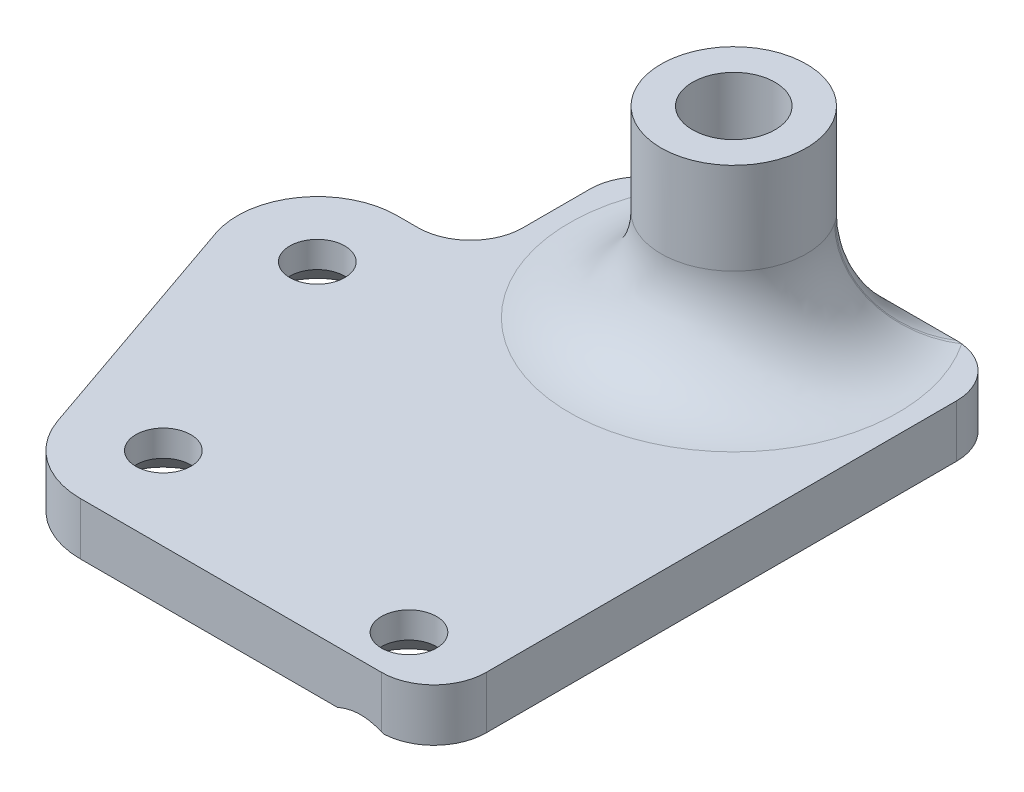
SolidWorks part; units mm, degrees
ref_plane "Front Plane" through (0, 0, 0) normal (0, 0, 1) x (1, 0, 0)
ref_plane "Top Plane" through (0, 0, 0) normal (0, 1, 0) x (1, 0, 0)
ref_plane "Right Plane" through (0, 0, 0) normal (1, 0, 0) x (0, 0, -1)
ref_axis "X-Axis" through (-88.4377, 0, 0) along (1, 0, 0)
ref_axis "Y-Axis" through (0, 0, -69.2525) along (0, 0, 1)
ref_axis "Z-Axis" through (0, -52.5493, 0) along (0, 1, 0)
sketch "Sketch1" plane through (0, 0, 0) normal (0, 1, 0) x (1, 0, 0)
  line L0 (0, 0) -> (-14, 0) construction
  line L4 (0, 0) -> (0, -10.5) construction
  line L5 (-16.8827, -0.9964) -> (-13.6961, -10.2156)
  line L6 (-11.2, 9.6) -> (2.8, 9.6)
  line L7 (-11.2, 9.6) -> (-11.2, 3.05)
  line L9 (2.8, 9.6) -> (2.8, 2.6)
  line L11 (-14, 3.05) -> (-11.2, 3.05)
  line L12 (2.8, -12.35) -> (2.8, 2.6)
  line L14 (-11.2, 9.6) -> (2.8, 2.6) construction
  line L15 (-10.7, -12.35) -> (2.8, -12.35)
  circle A0 centre (-14, 0) radius 1.05
  circle A2 centre (0, -10.5) radius 1.05
  circle A3 centre (-10.7, -9.18) radius 1.05
  arc A4 (-14, 3.05) -> (-16.8827, -0.9964) centre (-14, 0) ccw
  circle A7 centre (-14, 0) radius 3.05 construction
  arc A8 (-13.6961, -10.2156) -> (-10.7, -12.35) centre (-10.7, -9.18) ccw
  point P10 (-4.2, 6.1)
  point P14 (-4.2, 6.1)
  dimension "D5" = 2.1
  dimension "D9" = 9.8
  dimension "D1" = 14
  dimension "D2" = 10.5
  dimension "D3" = 10.7
  dimension "D4" = 1.32
  dimension "D6" = 14
  dimension "D7" = 3.5
  dimension "D10" = 6.1
  dimension "D11" = 1.85
  dimension "D8" = 2
extrude "Boss-Extrude1" add sketch "Sketch1" along normal blind 2
fillet "Fillet1" radius 2 4 edges at (2.8, 1, 12.35) (2.8, 1, -9.6) (-11.2, 1, -9.6) (-11.2, 1, -3.05)
sketch "Sketch2" plane through (0, 2, 0) normal (0, 1, 0) x (1, 0, 0)
  line L0 (-11.2, 9.6) -> (2.8, 2.6) construction
  circle A0 centre (-4.2, 6.1) radius 1.575
  circle A1 centre (-4.2, 6.1) radius 2.775
  dimension "D1" = 3.15
  dimension "D2" = 1.2
extrude "Boss-Extrude2" add sketch "Sketch2" along normal blind 7
fillet "Fillet2" radius 3.5 1 edges at (-4.2, 2, -3.325)
chamfer "Chamfer1" distance 1 angle 45 3 edges at (-10.7, 0, 10.23) (-14, 0, 1.05) (0, 0, 11.55)
